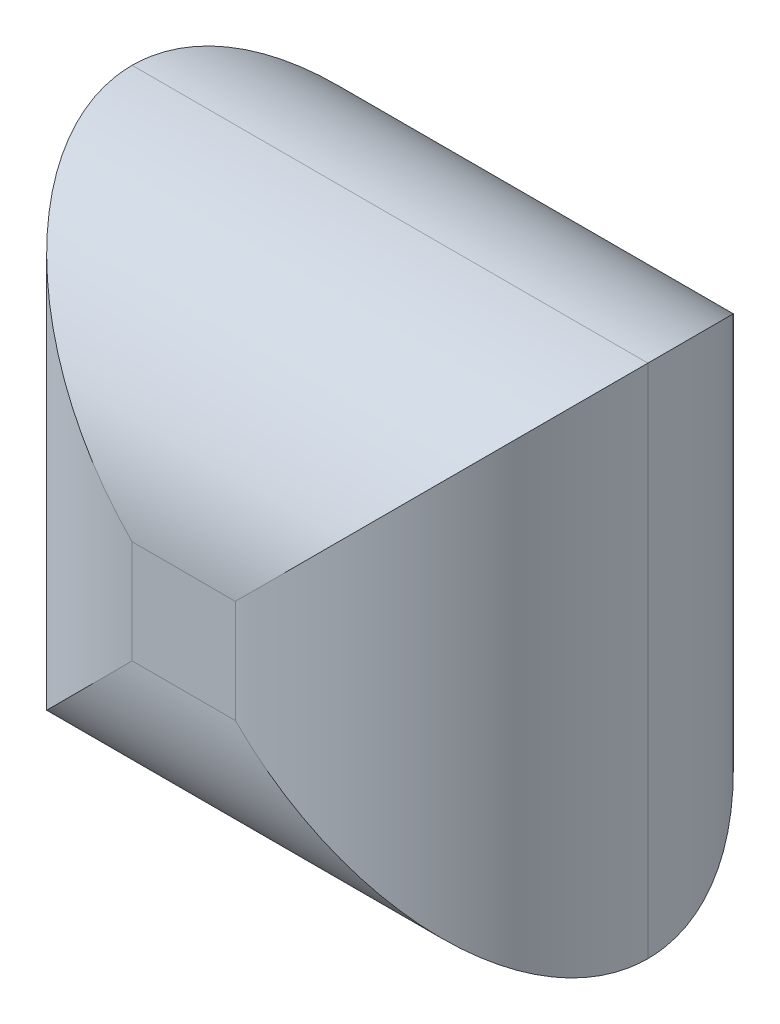
SolidWorks part; units mm, degrees
other "Parachute"
ref_plane "Front Plane" through (0, 0, 0) normal (0, 0, 1) x (1, 0, 0)
ref_plane "Top Plane" through (0, 0, 0) normal (0, 1, 0) x (1, 0, 0)
ref_plane "Right Plane" through (0, 0, 0) normal (1, 0, 0) x (0, 0, -1)
sketch "Sketch1" plane through (0, 0, 0) normal (0, 0, 1) x (1, 0, 0)
  line L1 (0, 0) -> (125, 0)
  line L2 (0, 0) -> (0, 125)
  line L3 (0, 125) -> (125, 125)
  line L4 (125, 0) -> (125, 125)
  dimension "D1" = 125
extrude "Boss-Extrude1" add sketch "Sketch1" along normal blind 100
fillet "Fillet1" radius 50 8 edges at (62.5, 0, 0) (125, 62.5, 0) (62.5, 125, 0) (0, 62.5, 0) (62.5, 125, 100) (125, 62.5, 100) (62.5, 0, 100) (0, 62.5, 100)
